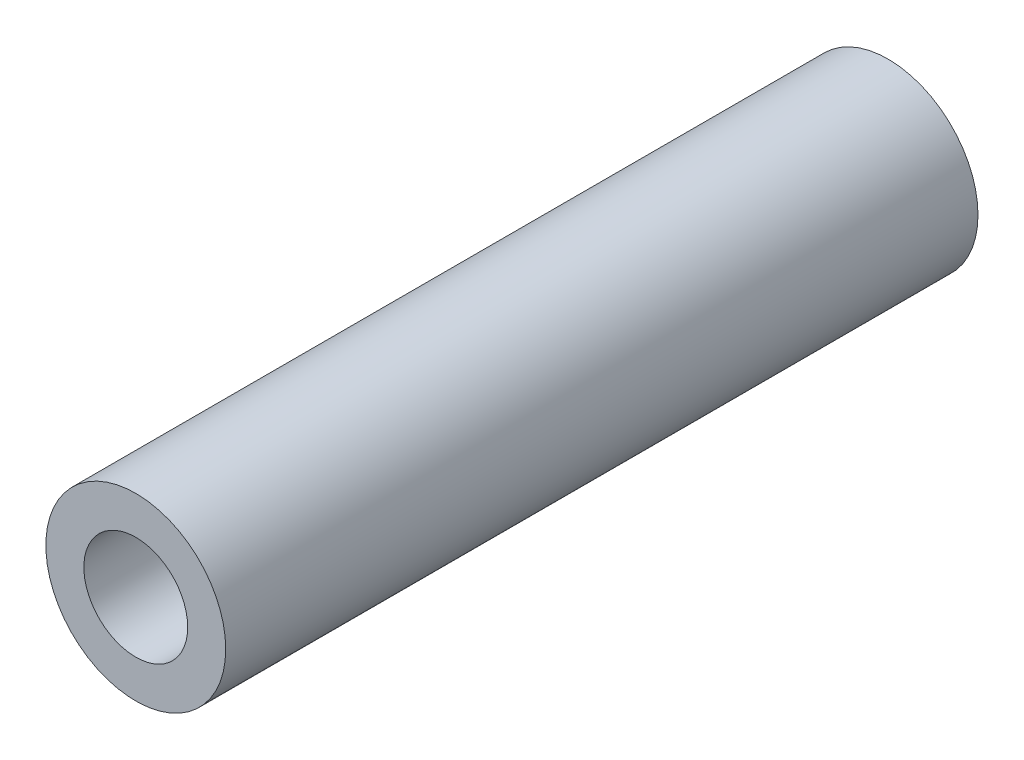
SolidWorks part; units mm, degrees
material "ABS"
ref_plane "Front Plane" through (0, 0, 0) normal (0, 0, 1) x (1, 0, 0)
ref_plane "Top Plane" through (0, 0, 0) normal (0, 1, 0) x (1, 0, 0)
ref_plane "Right Plane" through (0, 0, 0) normal (1, 0, 0) x (0, 0, -1)
sketch "Sketch1" plane through (0, 0, 0) normal (0, 0, 1) x (1, 0, 0)
  circle A0 centre (0, 0) radius 5.5
  circle A1 centre (0, 0) radius 3.175
  dimension "D1" = 6.35
  dimension "D2" = 11
extrude "Boss-Extrude1" add sketch "Sketch1" along normal mid plane 46
equation "\"D1@Sketch1\"=0.25in"
